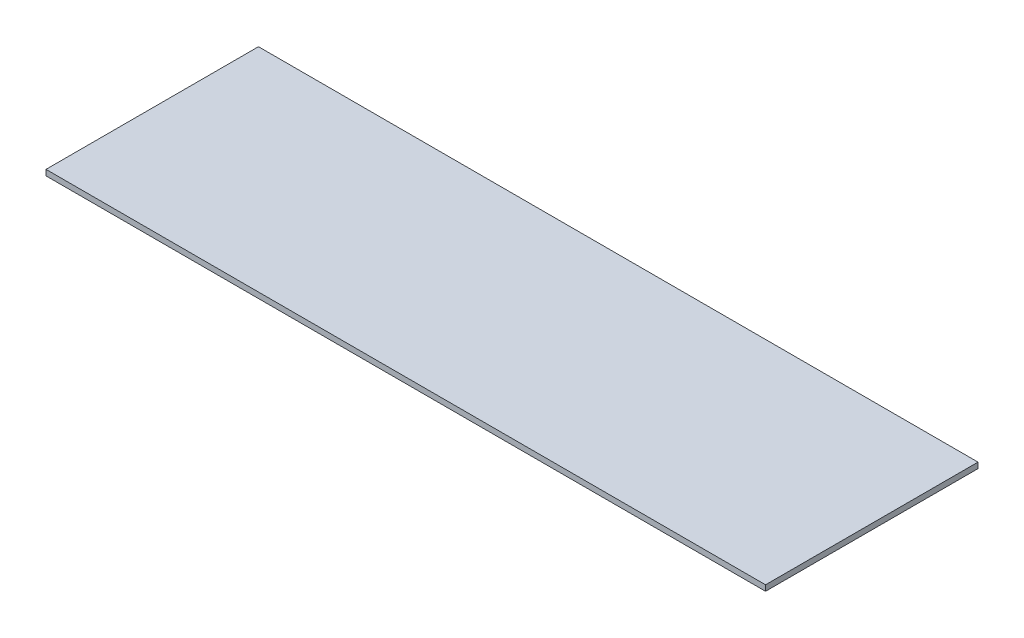
SolidWorks part; units mm, degrees
ref_plane "Front Plane" through (0, 0, 0) normal (0, 0, 1) x (1, 0, 0)
ref_plane "Top Plane" through (0, 0, 0) normal (0, 1, 0) x (1, 0, 0)
ref_plane "Right Plane" through (0, 0, 0) normal (1, 0, 0) x (0, 0, -1)
sketch "Sketch1" plane through (0, 0, 0) normal (0, 1, 0) x (1, 0, 0)
  line L1 (0, 0) -> (508, 0)
  line L2 (0, 0) -> (0, 150)
  line L3 (0, 150) -> (508, 150)
  line L4 (508, 0) -> (508, 150)
  dimension "D1" = 150
  dimension "D2" = 508
extrude "Boss-Extrude1" add sketch "Sketch1" along normal blind 4
equation "\"cf_tube_outer_diameter\" = 25mm"
equation "\"cf_tube_inner_diameter\" = 21mm"
equation "\"mid_plate_mid_to_top\" = 100mm"
equation "\"mid_plate_mid_to_bottom\" = 30mm"
equation "\"mid_plate_horizontal_spacing\" = 250mm"
equation "\"cf_plate_thickness\" = 4mm"
equation "\"mid_tube_length\" = 500mm"
equation "\"mid_plate_bottom_width\"= 150mm"
equation "\"D1@Sketch1\"=\"mid_plate_bottom_width\""
equation "\"D2@Sketch1\"=\"mid_tube_length\"+\"cf_plate_thickness\"*2"
equation "\"D1@Boss-Extrude1\"=\"cf_plate_thickness\""
